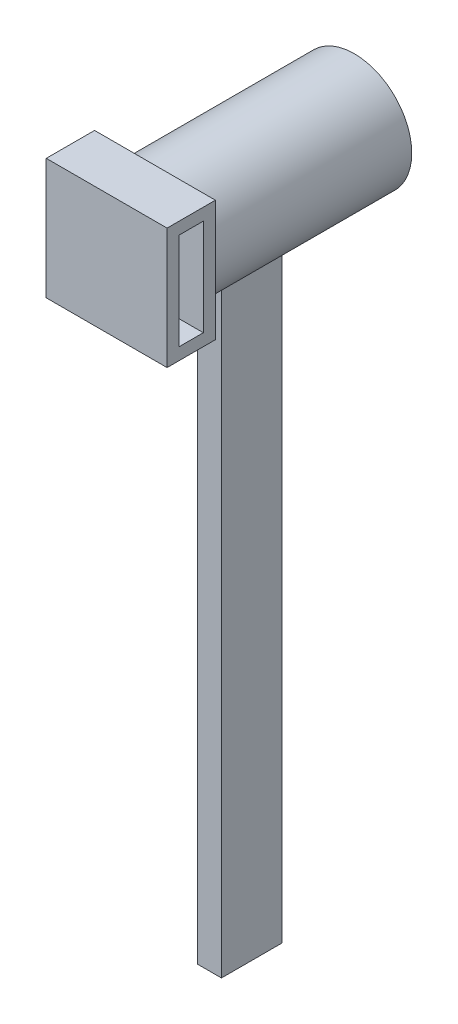
SolidWorks part; units mm, degrees
ref_plane "Front Plane" through (0, 0, 0) normal (0, 0, 1) x (1, 0, 0)
ref_plane "Top Plane" through (0, 0, 0) normal (0, 1, 0) x (1, 0, 0)
ref_plane "Right Plane" through (0, 0, 0) normal (1, 0, 0) x (0, 0, -1)
sketch "Sketch2" plane through (0, 0, 0) normal (0, 0, 1) x (1, 0, 0)
  circle A4 centre (0, 0) radius 4.75
  point P3 (25, 0)
  dimension "D1" = 9.5
ref_plane "Plane1" through (0, 0, 16.5) normal (0, 0, 1) x (1, 0, 0)
sketch "Sketch3" plane through (0, 0, 16.5) normal (0, 0, 1) x (1, 0, 0)
  line L0 (-5, 5) -> (5, 5)
  line L1 (-5, 5) -> (-5, -5)
  line L2 (-5, -5) -> (5, -5)
  line L3 (5, 5) -> (5, -5)
  circle A0 centre (0, 0) radius 4.75
  point P3 (0, 5)
  point P9 (5, 0)
  dimension "D1" = 9.5
  dimension "D2" = 10
loft "Loft1" add profiles "Sketch2", "Sketch3" connector at (0.4143, 4.7319, 0) connector at (0.1582, 4.7474, 16.5)
sketch "Sketch4" plane through (0, 0, 0) normal (0, 1, 0) x (1, 0, 0)
  line L1 (1, -12) -> (-1, -12)
  line L2 (1, -12) -> (1, -7)
  line L3 (1, -7) -> (-1, -7)
  line L4 (-1, -12) -> (-1, -7)
  line L7 (-4.75, 0) -> (-4.75, -16.5) construction
  line L8 (4.75, 0) -> (-4.75, 0) construction
  dimension "D1" = 7
  dimension "D2" = 3.75
  dimension "D3" = 5
  dimension "D4" = 2
extrude "Boss-Extrude1" add sketch "Sketch4" against normal blind 55
extrude "Boss-Extrude4" add sketch "Sketch3<7>" along normal blind 4 contours A0 L3 L0 L1 | A0 L1 L2 L3 | A0 | A0 L0 L1 | A0 L2 L3 region at (0, 4.8586, 16.5) region at (0, 0, 16.5)
sketch "Sketch3<7>" plane through (0, 0, 16.5) normal (0, 0, 1) x (1, 0, 0) same geometry as "Sketch3"
sketch "Sketch8" plane through (5, 0, 0) normal (1, 0, 0) x (0, 0, -1)
  line L0 (-20.5, 5) -> (-20.5, -5) construction
  line L1 (-19.5, 4) -> (-17.5, 4)
  line L2 (-19.5, 4) -> (-19.5, -4)
  line L3 (-19.5, -4) -> (-17.5, -4)
  line L4 (-17.5, 4) -> (-17.5, -4)
  line L5 (-20.5, 5) -> (-16.5, 5) construction
  point P4 (-19.5, 0)
  point P7 (-20.5, 0)
  point P8 (-18.5, 4)
  point P11 (-18.5, 5)
  dimension "D1" = 2
  dimension "D2" = 8
extrude "Cut-Extrude2" cut sketch "Sketch8" against normal through all both and the other way through all
